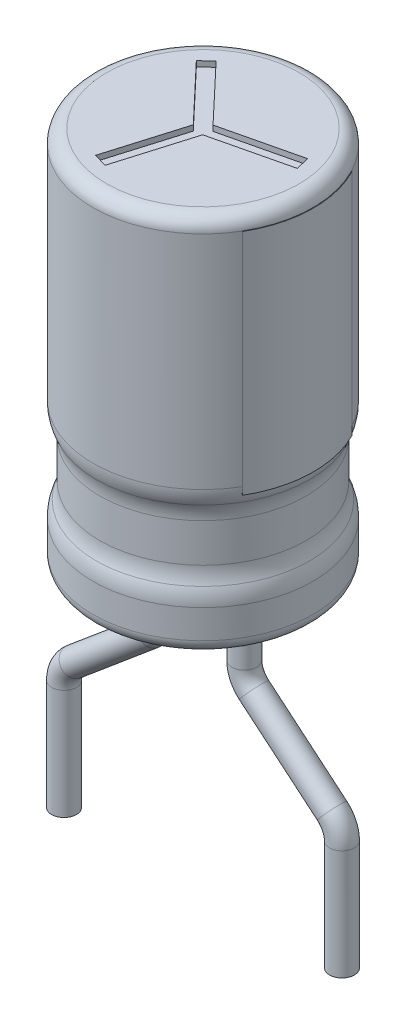
SolidWorks part; units mm, degrees
ref_plane "Front Plane" through (0, 0, 0) normal (0, 0, 1) x (1, 0, 0)
ref_plane "Top Plane" through (0, 0, 0) normal (0, 1, 0) x (1, 0, 0)
ref_plane "Right Plane" through (0, 0, 0) normal (1, 0, 0) x (0, 0, -1)
sketch "Sketch1" plane through (0, 0, 0) normal (0, 1, 0) x (1, 0, 0)
  circle A0 centre (0, 0) radius 2
  dimension "D1" = 4
extrude "Extrude1" add sketch "Sketch1" along normal blind 7
sketch "Sketch2" plane through (0, 7, 0) normal (0, 1, 0) x (-1, 0, 0)
  circle A0 centre (0, 0) radius 3.5
  dimension "D1" = 7
extrude "Cut-Extrude1" cut sketch "Sketch2" against normal blind 0.1
fillet "Fillet1" radius 0.25 2 edges at (0, 0, 2) (0, 6.9, 2)
ref_plane "Plane1" through (0, 1.7, 0) normal (0, 1, 0) x (-1, 0, 0)
sketch "Sketch3" plane through (0, 1.7, 0) normal (0, 1, 0) x (-1, 0, 0)
  circle A0 centre (0, 0) radius 1.875
  dimension "D1" = 3.75
extrude "Cut-Extrude2" cut sketch "Sketch3" against normal blind 0.75 and the other way blind 0.75 flip side to cut
fillet "Fillet2" radius 0.7 2 edges at (0, 0.95, 1.875) (0, 2.45, 1.875)
fillet "Fillet3" radius 0.7 2 edges at (0, 2.45, 2) (0, 0.95, 2)
sketch "Sketch4" plane through (0, 6.9, 0) normal (0, 1, 0) x (-1, 0, 0)
  line L0 (0, 0) -> (1.0309, -1.0896)
  line L1 (0, 0) -> (-1.4591, -0.348)
  line L2 (0, 0) -> (0.4281, 1.4376)
  dimension "D1" = 1.5
  dimension "D2" = 1.5
  dimension "D3" = 1.5
  dimension "D4" = 120
  dimension "D5" = 120
extrude "Cut-Extrude-Thin2" cut sketch "Sketch4" against normal blind 0.1 thin contours L0 thin type mid plane wall 0.254
extrude "Cut-Extrude-Thin3" cut sketch "Sketch4<3>" against normal blind 0.1 thin contours L1 thin type mid plane wall 0.254
sketch "Sketch4<3>" plane through (0, 6.9, 0) normal (0, 1, 0) x (-1, 0, 0) same geometry as "Sketch4"
extrude "Cut-Extrude-Thin4" cut sketch "Sketch4<4>" against normal blind 0.1 thin contours L2 thin type mid plane wall 0.254
sketch "Sketch4<4>" plane through (0, 6.9, 0) normal (0, 1, 0) x (-1, 0, 0) same geometry as "Sketch4"
sketch "Sketch5" plane through (0, 0, 0) normal (0, -1, 0) x (1, 0, 0)
  line L0 (-0.75, 0) -> (0.75, 0) construction
  circle A0 centre (-0.75, 0) radius 0.225
  circle A1 centre (0.75, 0) radius 0.225
  point P4 (0, 0)
  dimension "D1" = 0.45
  dimension "D2" = 1.5
extrude "Extrude2" add sketch "Sketch5" along normal blind 0.77
ref_plane "Board Plane" through (0, -0.5, 0) normal (0, 1, 0) x (-1, 0, 0)
sketch "Component_Outline" plane through (0, -0.5, 0) normal (0, 1, 0) x (-1, 0, 0)
  circle A0 centre (0, 0) radius 2
  circle A1 centre (0, 0) radius 2 construction
ref_plane "Plane4" through (0, 2.5, 0) normal (0, -1, 0) x (-1, 0, 0)
sketch "Sketch6" plane through (0, 2.5, 0) normal (0, 1, 0) x (1, 0, 0)
  line L0 (1.7606, 0.9058) -> (1.7873, 0.9196)
  line L1 (1.7089, -1.0001) -> (1.7348, -1.0152)
  arc A0 (1.7348, -1.0152) -> (1.7873, 0.9196) centre (0, 0) ccw
  arc A2 (1.7089, -1.0001) -> (1.7606, 0.9058) centre (0, 0) ccw
extrude "Boss-Extrude1" add sketch "Sketch6" along normal blind 4.15
ref_plane "Plane3" through (0, -0.77, 0) normal (0, -1, 0) x (-1, 0, 0)
sketch "Sketch8" plane through (0, -2, 0) normal (0, 0, -1) x (1, 0, 0)
  line L0 (0.9286, -0.5242) -> (2.3458, 0.6649)
  line L1 (2.5244, 1.0479) -> (2.5244, 3.0479)
  line L3 (0.75, -1.23) -> (0.75, -0.9073)
  line L4 (0.975, -1.23) -> (0.525, -1.23) construction
  arc A0 (0.9286, -0.5242) -> (0.75, -0.9073) centre (1.25, -0.9073) ccw
  arc A1 (2.3458, 0.6649) -> (2.5244, 1.0479) centre (2.0244, 1.0479) ccw
  dimension "D1" = 0.5
sketch "Sketch9" plane through (0, -0.77, -4.6569) normal (0, 1, 0) x (1, 0, 0)
  circle A0 centre (0.75, -4.6569) radius 0.225
  circle A1 centre (0.75, -4.6569) radius 0.225 construction
sweep "Sweep2" add profiles "Sketch9" path "Sketch8"
mirror "Mirror1" about plane through (0, 0, 0) normal (1, 0, 0) of "Sweep2"
